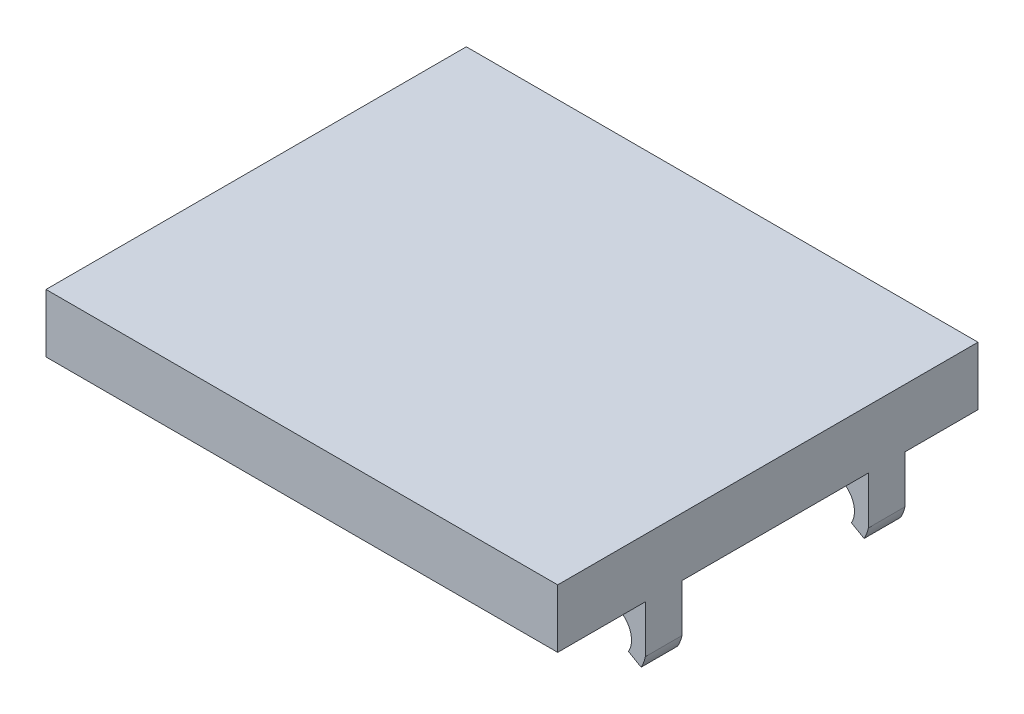
SolidWorks part; units mm, degrees
ref_plane "Front Plane" through (0, 0, 0) normal (0, 0, 1) x (1, 0, 0)
ref_plane "Top Plane" through (0, 0, 0) normal (0, 1, 0) x (1, 0, 0)
ref_plane "Right Plane" through (0, 0, 0) normal (1, 0, 0) x (0, 0, -1)
ref_plane "Plane5" through (0, 1.4, 0) normal (0, 1, 0) x (1, 0, 0)
sketch "Sketch1" plane through (0, 1.4, 0) normal (0, 1, 0) x (1, 0, 0)
  line L0 (-30, 40.97) -> (30, 40.97) construction
  line L1 (35, -16.53) -> (-35, -16.53)
  line L2 (35, -16.53) -> (35, 40.97)
  line L3 (35, 40.97) -> (-35, 40.97)
  line L4 (-35, -16.53) -> (-35, 40.97)
  line L5 (35, -16.53) -> (-35, 40.97) construction
  line L6 (35, 40.97) -> (-35, -16.53) construction
  line L8 (45.85, -16.53) -> (-45.85, -16.53) construction
  line L9 (0, 0) -> (0, 83.8599) construction
  point P0 (-14.8765, 0)
  point P13 (0, 12.22)
  dimension "D1" = 70
extrude "Boss-Extrude1" add sketch "Sketch1" along normal blind 8
sketch "Sketch3" plane through (0, 0, -40.97) normal (0, 0, -1) x (-1, 0, 0)
  line L0 (-35, 1.4) -> (-35, -5.105)
  line L1 (-24.9, -4.1) -> (-24.9, 1.4)
  line L2 (0, 0) -> (0, -23.3047) construction
  line L3 (-35, 1.4) -> (-24.9, 1.4)
  line L4 (-35, 1.4) -> (35, 1.4) construction
  line L5 (35, 1.4) -> (24.9, 1.4)
  line L6 (35, 1.4) -> (35, -5.105)
  line L7 (24.9, -4.1) -> (24.9, 1.4)
  arc A0 (-35, -3.095) -> (-24.9, -4.1) centre (-30, -4.1) ccw
  circle A2 centre (-30, -4.1) radius 3.1
  arc A4 (35, -3.095) -> (24.9, -4.1) centre (30, -4.1) cw
  circle A5 centre (30, -4.1) radius 3.1
  line M2 (-35, 1.4) -> (35, 1.4)
  dimension "D1" = 2
  dimension "D2" = 6.2
extrude "Boss-Extrude2" add sketch "Sketch3" against normal blind 5 from offset 10 contours L0 A0 L1 A2 M2 | A4 L6 L7 A5 M2 region at (29.95, 1.2536, -40.97) region at (-29.95, 1.2536, -40.97) offset against normal yes
ref_plane "Plane1" through (0, 0, -13.22) normal (0, 0, 1) x (1, 0, 0)
mirror "Mirror1" about plane through (0, 0, -13.22) normal (0, 0, 1) of "Boss-Extrude2"
sketch "Sketch4" plane through (0, 0, -30.97) normal (0, 0, 1) x (1, 0, 0)
  line L0 (30, -4.1) -> (40, -9.8735)
  line L1 (40, -9.8735) -> (20, -9.8735)
  line L2 (20, -9.8735) -> (30, -4.1)
  line L3 (0, 0) -> (0, -31.947) construction
  line L4 (-40, -9.8735) -> (-20, -9.8735)
  line L5 (-30, -4.1) -> (-40, -9.8735)
  line L6 (-20, -9.8735) -> (-30, -4.1)
  dimension "D1" = 20
  dimension "D2" = 120
extrude "Cut-Extrude1" cut sketch "Sketch4" along normal blind 63
sketch "Sketch5" plane through (0, 0, 16.53) normal (0, 0, 1) x (1, 0, 0)
  line L0 (35, 8.9) -> (35.5, 8.9)
  line L1 (35, 0.9) -> (41.7832, 5.6157)
  line L2 (35, 0.9) -> (35, 8.9)
  arc A0 (41.7832, 5.6157) -> (35.5, 8.9) centre (39.5, 8.9) ccw
  circle A1 centre (39.5, 8.9) radius 4 construction
  dimension "D2" = 8
  dimension "D1" = 4.5
extrude "Boss-Extrude3" [suppressed] add sketch "Sketch5" against normal blind 5 separate body
sketch "Sketch6" [suppressed] plane through (0, 0, 36.97) normal (0, 0, -1) x (-1, 0, 0)
  circle A0 centre (-39.5, 8) radius 2
  dimension "D1" = 4
extrude "Boss-Extrude4" [suppressed] add sketch "Sketch6" along normal blind 3.8 draft 14
fillet "Fillet1" [suppressed] radius 1
ref_plane "Plane2" [suppressed] through (0, 4, 0) normal (0, -1, 0) x (-1, 0, 0)
mirror "Mirror2" [suppressed] about plane through (0, 4, 0) normal (0, -1, 0) of bodies 106
delete or keep bodies "Body-Delete/Keep 1" [suppressed] type delete bodies bodies 106
ref_plane "Plane3" [suppressed] through (0, 0, 0) normal (0, 0, 1) x (1, 0, 0)
mirror "Mirror3" [suppressed] about plane through (0, 0, 0) normal (0, 0, 1) of bodies 107
ref_plane "Plane4" [suppressed] through (0, 0, 0) normal (-1, 0, 0) x (0, 0, 1)
mirror "Mirror4" [suppressed] about plane through (0, 0, 0) normal (-1, 0, 0) of bodies 107 108
combine bodies "Combine1" [suppressed] operation type add bodies to combine 110 104 109 107 108
